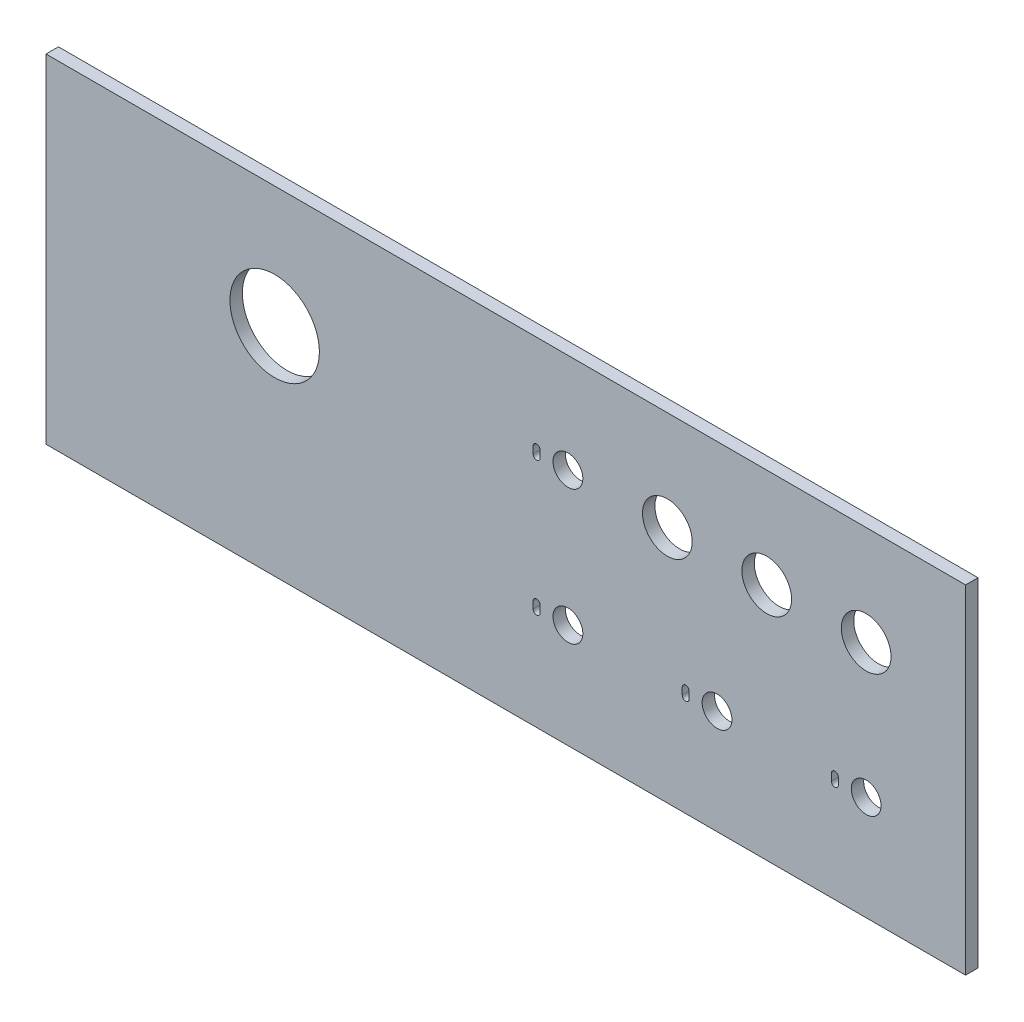
SolidWorks part; units mm, degrees
material "Acrylic (Medium-high impact)"
ref_plane "Front Plane" through (0, 0, 0) normal (0, 0, 1) x (1, 0, 0)
ref_plane "Top Plane" through (0, 0, 0) normal (0, 1, 0) x (1, 0, 0)
ref_plane "Right Plane" through (0, 0, 0) normal (1, 0, 0) x (0, 0, -1)
sketch "Sketch1" plane through (0, 0, 0) normal (0, 0, 1) x (1, 0, 0)
  line L1 (-117.475, -43.18) -> (117.475, -43.18)
  line L2 (-117.475, -43.18) -> (-117.475, 43.18)
  line L3 (-117.475, 43.18) -> (117.475, 43.18)
  line L4 (117.475, -43.18) -> (117.475, 43.18)
  line L5 (-117.475, -43.18) -> (117.475, 43.18) construction
  line L6 (-117.475, 43.18) -> (117.475, -43.18) construction
  point P0 (0, 0)
  dimension "D1" = 86.36
  dimension "D2" = 234.95
base flange "Base-Flange1" sketch "Sketch1" thickness 3.175 reverse thickness direction no parameters "D1"=3
edge flange "Edge-Flange1" [suppressed] sketch "Sketch8" flange angle 90 bend radius 3 thickness 3.175
sketch "Sketch8" plane through (0, -43.18, -3.175) normal (0, -1, 0) x (-1, 0, 0)
  line L0 (117.475, 0) -> (-117.475, 0) construction
  line L1 (117.475, 0) -> (-117.475, 0)
  line L2 (-117.475, 0) -> (-117.475, 15.875)
  line L3 (-117.475, 15.875) -> (117.475, 15.875)
  line L4 (117.475, 15.875) -> (117.475, 0)
bend "EdgeBend1" bend radius 3 bend angle 90 parameters "D5"=1, "D6"=10, "D7"=19.05
sketch "Sketch10" [suppressed] plane through (0, -43.18, 0) normal (0, -1, 0) x (1, 0, 0)
  line L0 (-117.475, -19.05) -> (117.475, -19.05) construction
  line L7 (-117.475, -3.175) -> (117.475, -3.175) construction
  line L8 (-117.475, -3.175) -> (117.475, -3.175) construction
  circle A0 centre (-63.5, -12.7) radius 3.9688
  dimension "D1" = 7.9375
  dimension "D2" = 6.35
extrude "Cut-Extrude2" [suppressed] cut sketch "Sketch10" against normal through all
sketch "Sketch15" [suppressed] plane through (0, -43.18, 0) normal (0, -1, 0) x (1, 0, 0)
  line L1 (-117.475, -19.05) -> (-112.649, -19.05)
  line L2 (-117.475, -19.05) -> (-117.475, -3.175)
  line L3 (-117.475, -3.175) -> (-112.649, -3.175)
  line L4 (-112.649, -19.05) -> (-112.649, -3.175)
  line L5 (-117.475, -3.175) -> (117.475, -3.175) construction
  line L6 (-117.475, -3.175) -> (117.475, -3.175) construction
  point P7 (-115.062, -3.175)
  dimension "D1" = 4.826
extrude "Cut-Extrude7" [suppressed] cut sketch "Sketch15" against normal through all
mirror "Mirror1" [suppressed] about plane through (0, 0, 0) normal (1, 0, 0)
sketch "Sketch11" plane through (0, 0, 0) normal (0, 0, 1) x (1, 0, 0)
  line L2 (41.275, 17.78) -> (92.075, 17.78) construction
  line L3 (117.475, 43.18) -> (-117.475, 43.18) construction
  line L4 (117.475, -43.18) -> (117.475, 43.18) construction
  circle A0 centre (41.275, 17.78) radius 6.35
  circle A1 centre (66.675, 17.78) radius 6.35
  circle A2 centre (92.075, 17.78) radius 6.35
  point P11 (66.675, 17.78)
  dimension "D3" = 12.7
  dimension "D1" = 25.4
  dimension "D2" = 25.4
  dimension "D4" = 25.4
extrude "Cut-Extrude3" cut sketch "Sketch11" against normal through all normal cut yes
sketch "Sketch12" plane through (0, 0, 0) normal (0, 0, 1) x (1, 0, 0)
  line L0 (15.875, -16.51) -> (92.075, -16.51) construction
  line L1 (7.874, -15.621) -> (7.874, -17.399) construction
  line L2 (8.763, -15.621) -> (8.763, -17.399)
  line L3 (6.985, -15.621) -> (6.985, -17.399)
  line L4 (19.685, -16.51) -> (19.685, -7.3196) construction
  line L5 (12.065, -16.51) -> (12.065, -8.1363) construction
  line L6 (45.974, -15.621) -> (45.974, -17.399) construction
  line L7 (46.863, -15.621) -> (46.863, -17.399)
  line L8 (45.085, -15.621) -> (45.085, -17.399)
  line L9 (84.074, -15.621) -> (84.074, -17.399) construction
  line L10 (84.963, -15.621) -> (84.963, -17.399)
  line L11 (83.185, -15.621) -> (83.185, -17.399)
  circle A0 centre (92.075, -16.51) radius 3.81
  circle A1 centre (53.975, -16.51) radius 3.81
  circle A2 centre (15.875, -16.51) radius 3.81
  circle A3 centre (41.275, 17.78) radius 6.35 construction
  circle A4 centre (41.275, 17.78) radius 6.35 construction
  arc A5 (8.763, -15.621) -> (6.985, -15.621) centre (7.874, -15.621) ccw
  arc A6 (6.985, -17.399) -> (8.763, -17.399) centre (7.874, -17.399) ccw
  arc A7 (46.863, -15.621) -> (45.085, -15.621) centre (45.974, -15.621) ccw
  arc A8 (45.085, -17.399) -> (46.863, -17.399) centre (45.974, -17.399) ccw
  arc A9 (84.963, -15.621) -> (83.185, -15.621) centre (84.074, -15.621) ccw
  arc A10 (83.185, -17.399) -> (84.963, -17.399) centre (84.074, -17.399) ccw
  circle A11 centre (92.075, 17.78) radius 6.35 construction
  circle A12 centre (92.075, 17.78) radius 6.35 construction
  point P7 (53.975, -16.51)
  point P11 (7.874, -16.51)
  point P19 (7.874, -14.732)
  point P20 (7.874, -18.288)
  point P25 (45.974, -16.51)
  point P32 (84.074, -16.51)
  dimension "D4" = 7.62
  dimension "D3" = 1.778
  dimension "D5" = 3.556
  dimension "D1" = 38.1
  dimension "D2" = 8.001
  dimension "D6" = 12.7
  dimension "D7" = 3.302
  dimension "D8" = 8.001
  dimension "D9" = 8.001
  dimension "D10" = 34.29
extrude "Cut-Extrude4" cut sketch "Sketch12" against normal through all normal cut yes
sketch "Sketch13" plane through (0, 0, 0) normal (0, 0, 1) x (1, 0, 0)
  line L0 (-117.475, 43.18) -> (-117.475, -43.18) construction
  line L1 (117.475, 43.18) -> (-117.475, 43.18) construction
  circle A0 centre (-59.055, 12.192) radius 11.43
  dimension "D2" = 22.86
  dimension "D1" = 58.42
  dimension "D3" = 30.988
extrude "Cut-Extrude5" cut sketch "Sketch13" against normal through all normal cut yes
sketch "Sketch14" plane through (0, 0, 0) normal (0, 0, 1) x (1, 0, 0)
  line L0 (45.085, -15.621) -> (45.085, -17.399) construction
  line L1 (46.863, -17.399) -> (46.863, -15.621) construction
  line L2 (45.085, -15.621) -> (45.085, -17.399) construction
  line L3 (46.863, -17.399) -> (46.863, -15.621) construction
  line L4 (7.874, 18.669) -> (7.874, 16.891) construction
  line L5 (8.763, 18.669) -> (8.763, 16.891)
  line L6 (6.985, 18.669) -> (6.985, 16.891)
  circle A0 centre (53.975, -16.51) radius 3.81 construction
  circle A1 centre (53.975, -16.51) radius 3.81 construction
  circle A2 centre (15.875, 17.78) radius 3.81
  arc A3 (45.085, -17.399) -> (46.863, -17.399) centre (45.974, -17.399) ccw construction
  arc A4 (46.863, -15.621) -> (45.085, -15.621) centre (45.974, -15.621) ccw construction
  arc A5 (45.085, -17.399) -> (46.863, -17.399) centre (45.974, -17.399) ccw construction
  arc A6 (46.863, -15.621) -> (45.085, -15.621) centre (45.974, -15.621) ccw construction
  arc A7 (8.763, 18.669) -> (6.985, 18.669) centre (7.874, 18.669) ccw
  arc A8 (6.985, 16.891) -> (8.763, 16.891) centre (7.874, 16.891) ccw
  circle A9 centre (15.875, -16.51) radius 3.81 construction
  circle A10 centre (15.875, -16.51) radius 3.81 construction
  circle A11 centre (41.275, 17.78) radius 6.35 construction
  circle A12 centre (41.275, 17.78) radius 6.35 construction
  point P13 (7.874, 17.78)
  dimension "D2" = 8.001
  dimension "D3" = 8.001
extrude "Cut-Extrude6" cut sketch "Sketch14" against normal through all normal cut yes
sketch "Bend-Lines1" [suppressed] plane through (0, 0, 0) normal (0, 1, 0) x (1, 0, 0)
sketch "Bounding-Box1" [suppressed] plane through (0, 0, 0) normal (0, 1, 0) x (1, 0, 0)
sheet metal parameters "Sheet-Metal1" thickness 3.175 parameters "D1"=3
flat pattern "Flat-Pattern1" [suppressed]
sketch "Bend-Lines2" plane through (0, 0, 0) normal (0, 1, 0) x (1, 0, 0)
sketch3d "Bounding-Box2" [suppressed]
  line L0 (117.475, -38.1, 0) -> (-117.475, -38.1, 0) construction
  line L1 (117.475, 38.1, 0) -> (-117.475, 38.1, 0) construction
  line L2 (117.475, -38.1, 0) -> (117.475, 38.1, 0) construction
  line L3 (-117.475, -38.1, 0) -> (-117.475, 38.1, 0) construction
sheet metal parameters "Sheet-Metal2" thickness 3.175 parameters "D1"=3
flat pattern "Flat-Pattern1"
sketch "Bend-Lines2" plane through (0, 0, 0) normal (0, 0, 1) x (1, 0, 0)
  line L0 (-117.475, -35.528) -> (117.475, -35.528) construction
  line L1 (-117.475, -35.528) -> (117.475, -35.528) construction
sketch3d "Bounding-Box2" [suppressed]
  line L0 (-117.475, -52.006, 0) -> (117.475, -52.006, 0) construction
  line L1 (-117.475, 38.1, 0) -> (117.475, 38.1, 0) construction
  line L2 (-117.475, -52.006, 0) -> (-117.475, 38.1, 0) construction
  line L3 (117.475, -52.006, 0) -> (117.475, 38.1, 0) construction
bend of the flat pattern "Flatten-<EdgeBend1>1"
sheet metal parameters "Sheet-Metal5" thickness 3.175 parameters "D1"=3
flat pattern "Flat-Pattern1" [suppressed]
sketch "Bend-Lines2" plane through (0, 0, 0) normal (0, 0, 1) x (1, 0, 0)
  line L0 (-112.7125, -38.703) -> (117.475, -38.703) construction
  line L1 (-112.7125, -38.703) -> (117.475, -38.703) construction
sketch3d "Bounding-Box2" [suppressed]
  line L0 (-117.475, -55.181, 0) -> (117.475, -55.181, 0) construction
  line L1 (-117.475, 41.275, 0) -> (117.475, 41.275, 0) construction
  line L2 (-117.475, -55.181, 0) -> (-117.475, 41.275, 0) construction
  line L3 (117.475, -55.181, 0) -> (117.475, 41.275, 0) construction
bend of the flat pattern "Flatten-<EdgeBend1>1"
sketch "Sketch10-1" [suppressed] plane through (0, -36.131, 0) normal (0, 0, 1) x (1, 0, 0)
  line L0 (-112.7125, -19.05) -> (117.475, -19.05) construction
  line L2 (-117.475, -19.05) -> (-112.7125, -19.05)
  line L3 (-117.475, -19.05) -> (-117.475, -3.175)
  line L4 (-117.475, -3.175) -> (-112.7125, -3.175)
  line L5 (-112.7125, -19.05) -> (-112.7125, -3.175)
  line L8 (-117.475, -3.175) -> (117.475, -3.175) construction
  circle A0 centre (-73.5966, -12.7) radius 3.9688
  dimension "D1" = 7.9375
  dimension "D2" = 6.35
  dimension "D3" = 4.7625
sheet metal parameters "Sheet-Metal9" thickness 3.175 parameters "D1"=3
flat pattern "Flat-Pattern1" [suppressed]
sketch "Bend-Lines2" plane through (0, 0, 0) normal (0, 0, 1) x (1, 0, 0)
  line L0 (-112.7125, -39.6555) -> (112.7125, -39.6555) construction
  line L1 (-112.7125, -39.6555) -> (112.7125, -39.6555) construction
sketch3d "Bounding-Box2" [suppressed]
  line L0 (-117.475, -56.1335, 0) -> (117.475, -56.1335, 0) construction
  line L1 (-117.475, 42.2275, 0) -> (117.475, 42.2275, 0) construction
  line L2 (-117.475, -56.1335, 0) -> (-117.475, 42.2275, 0) construction
  line L3 (117.475, -56.1335, 0) -> (117.475, 42.2275, 0) construction
bend of the flat pattern "Flatten-<EdgeBend1>1"
sketch "Sketch10-1" plane through (0, -37.0835, 0) normal (0, 0, 1) x (1, 0, 0)
  line L0 (-112.7125, -19.05) -> (112.7125, -19.05) construction
  line L2 (-117.475, -19.05) -> (-112.7125, -19.05)
  line L3 (-117.475, -19.05) -> (-117.475, -3.175)
  line L4 (-117.475, -3.175) -> (-112.7125, -3.175)
  line L5 (-112.7125, -19.05) -> (-112.7125, -3.175)
  line L8 (-117.475, -3.175) -> (117.475, -3.175) construction
  circle A0 centre (-63.5, -12.7) radius 3.9688
  dimension "D1" = 7.9375
  dimension "D2" = 6.35
  dimension "D3" = 4.7625
  dimension "D4" = 53.975
sheet metal parameters "Sheet-Metal10" thickness 3.175 parameters "D1"=3
flat pattern "Flat-Pattern1" [suppressed]
sketch "Bend-Lines2" plane through (0, 0, 0) normal (0, 0, 1) x (1, 0, 0)
  line L0 (-112.7125, -40.608) -> (112.7125, -40.608) construction
  line L1 (-112.7125, -40.608) -> (112.7125, -40.608) construction
sketch3d "Bounding-Box2" [suppressed]
  line L0 (-117.475, -57.086, 0) -> (117.475, -57.086, 0) construction
  line L1 (-117.475, 43.18, 0) -> (117.475, 43.18, 0) construction
  line L2 (-117.475, -57.086, 0) -> (-117.475, 43.18, 0) construction
  line L3 (117.475, -57.086, 0) -> (117.475, 43.18, 0) construction
sketch "Sketch10-1" plane through (0, -38.036, 0) normal (0, 0, 1) x (1, 0, 0)
  line L0 (-112.7125, -19.05) -> (112.7125, -19.05) construction
  line L2 (-117.475, -19.05) -> (-112.7125, -19.05)
  line L3 (-117.475, -19.05) -> (-117.475, -3.175)
  line L4 (-117.475, -3.175) -> (-112.7125, -3.175)
  line L5 (-112.7125, -19.05) -> (-112.7125, -3.175)
  line L8 (-117.475, -3.175) -> (117.475, -3.175) construction
  circle A0 centre (-63.5, -12.7) radius 3.9688
  dimension "D1" = 7.9375
  dimension "D2" = 6.35
  dimension "D3" = 4.7625
  dimension "D4" = 53.975
sheet metal parameters "Sheet-Metal11" thickness 3.175 parameters "D1"=3
flat pattern "Flat-Pattern1" [suppressed]
sketch "Bend-Lines2" plane through (0, 0, 0) normal (0, 0, 1) x (1, 0, 0)
  line L0 (-112.7125, -40.608) -> (112.7125, -40.608) construction
  line L1 (-112.7125, -40.608) -> (112.7125, -40.608) construction
sketch3d "Bounding-Box2" [suppressed]
  line L0 (-117.475, -57.086, 0) -> (117.475, -57.086, 0) construction
  line L1 (-117.475, 43.18, 0) -> (117.475, 43.18, 0) construction
  line L2 (-117.475, -57.086, 0) -> (-117.475, 43.18, 0) construction
  line L3 (117.475, -57.086, 0) -> (117.475, 43.18, 0) construction
sketch "Sketch10-1" plane through (0, -38.036, 0) normal (0, 0, 1) x (1, 0, 0)
  line L0 (-112.7125, -19.05) -> (112.7125, -19.05) construction
  line L2 (-117.475, -19.05) -> (-112.7125, -19.05)
  line L3 (-117.475, -19.05) -> (-117.475, -3.175)
  line L4 (-117.475, -3.175) -> (-112.7125, -3.175)
  line L5 (-112.7125, -19.05) -> (-112.7125, -3.175)
  line L8 (-117.475, -3.175) -> (117.475, -3.175) construction
  circle A0 centre (-63.5, -12.7) radius 3.9688
  dimension "D1" = 7.9375
  dimension "D2" = 6.35
  dimension "D3" = 4.7625
  dimension "D4" = 53.975
sheet metal parameters "Sheet-Metal12" thickness 3.175 parameters "D1"=3
flat pattern "Flat-Pattern1"
sketch "Bend-Lines2" plane through (0, 0, 0) normal (0, 0, 1) x (1, 0, 0)
sketch3d "Bounding-Box2" [suppressed]
  line L0 (-117.475, -43.18, 0) -> (117.475, -43.18, 0) construction
  line L1 (-117.475, 43.18, 0) -> (117.475, 43.18, 0) construction
  line L2 (-117.475, -43.18, 0) -> (-117.475, 43.18, 0) construction
  line L3 (117.475, -43.18, 0) -> (117.475, 43.18, 0) construction
sheet metal parameters "Sheet-Metal13" thickness 3.175 parameters "D1"=3
flat pattern "Flat-Pattern1"
sketch "Bend-Lines2" plane through (0, 0, 0) normal (0, 0, 1) x (1, 0, 0)
sketch3d "Bounding-Box2" [suppressed]
  line L0 (-117.475, -43.18, 0) -> (117.475, -43.18, 0) construction
  line L1 (-117.475, 43.18, 0) -> (117.475, 43.18, 0) construction
  line L2 (-117.475, -43.18, 0) -> (-117.475, 43.18, 0) construction
  line L3 (117.475, -43.18, 0) -> (117.475, 43.18, 0) construction
sheet metal parameters "Sheet-Metal14" thickness 3.175 parameters "D1"=3
flat pattern "Flat-Pattern1" [suppressed]
sketch "Bend-Lines2" plane through (0, 0, 0) normal (0, 0, 1) x (1, 0, 0)
  line L0 (-112.649, -40.608) -> (117.475, -40.608) construction
  line L1 (-112.649, -40.608) -> (117.475, -40.608) construction
sketch3d "Bounding-Box2" [suppressed]
  line L0 (-117.475, -57.086, 0) -> (117.475, -57.086, 0) construction
  line L1 (-117.475, 43.18, 0) -> (117.475, 43.18, 0) construction
  line L2 (-117.475, -57.086, 0) -> (-117.475, 43.18, 0) construction
  line L3 (117.475, -57.086, 0) -> (117.475, 43.18, 0) construction
bend of the flat pattern "Flatten-<EdgeBend1>1"
sketch "Sketch10-1" plane through (0, -38.036, 0) normal (0, 0, 1) x (1, 0, 0)
  line L0 (-112.649, -19.05) -> (117.475, -19.05) construction
  line L8 (-117.475, -3.175) -> (117.475, -3.175) construction
  circle A0 centre (-63.5, -12.7) radius 3.9688
  dimension "D1" = 7.9375
  dimension "D2" = 6.35
equation "\"D3@Sketch14\"=\"D2@Sketch14\""
